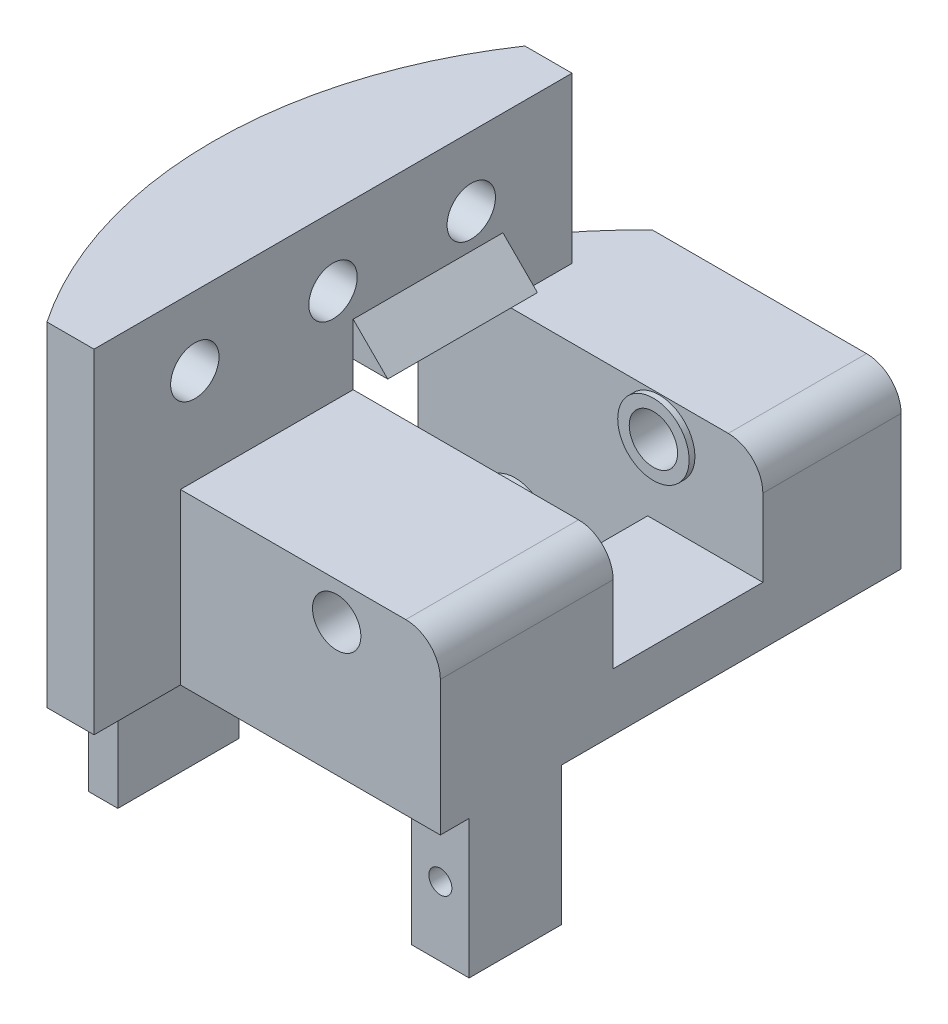
SolidWorks part; units mm, degrees
note: The reader was unsure of these and kept them because the rebuilt part matched: shared geometry of "Sketch24<2>".
material "Custom Plastic"
ref_plane "Front Plane" through (0, 0, 0) normal (0, 0, 1) x (1, 0, 0)
ref_plane "Top Plane" through (0, 0, 0) normal (0, 1, 0) x (1, 0, 0)
ref_plane "Right Plane" through (0, 0, 0) normal (1, 0, 0) x (0, 0, -1)
sketch "Sketch1" plane through (0, 0, 0) normal (0, 1, 0) x (1, 0, 0)
  line L12 (-36.9789, 1.25) -> (-36.9789, -1.25)
  line L13 (-36.9789, -1.25) -> (-31.9789, -1.25)
  line L14 (-31.9789, -1.25) -> (-31.9789, -17.25)
  line L15 (-31.9789, -17.25) -> (-8.9789, -17.25)
  line L16 (-8.9789, -17.25) -> (-8.9789, -1.25)
  line L17 (-8.9789, -1.25) -> (-3.9789, -1.25)
  line L18 (-3.9789, -1.25) -> (-3.9789, 1.25)
  line L19 (-3.9789, 1.25) -> (-8.9789, 1.25)
  line L20 (-8.9789, 1.25) -> (-8.9789, 5.25)
  line L21 (-8.9789, 5.25) -> (-31.9789, 5.25)
  line L22 (-31.9789, 5.25) -> (-31.9789, 1.25)
  line L23 (-31.9789, 1.25) -> (-36.9789, 1.25)
  line L24 (-31.9789, -17.25) -> (-32.7328, -17.25)
  line L25 (-8.9789, -9.25) -> (-3.9789, -9.25)
  line L26 (-3.9789, -9.25) -> (-3.9789, -1.25)
  line L27 (-34.5462, -13.25) -> (-31.9789, -13.25)
  circle A0 centre (0, 0) radius 37
  point P4 (-37, 0)
  point P15 (-36.9789, 0)
  dimension "D1" = 74
  dimension "D2" = 2.5
  dimension "D3" = 4
  dimension "D4" = 16
  dimension "D5" = 5
  dimension "D6" = 5
  dimension "D7" = 23
  dimension "D8" = 5
  dimension "D9" = 8
  dimension "D10" = 12
extrude "Boss-Extrude1" add sketch "Sketch1" along normal blind 12 contours L13 A0 L24 L14 | L25 L26 L17 L16
sketch "Sketch2" plane through (0, 12, 0) normal (0, 1, 0) x (1, 0, 0)
  line L3 (-3.9789, -13.25) -> (-3.9789, 1.75)
  line L6 (-3.9789, 1.75) -> (-36.9586, 1.75)
  line L7 (-34.5462, -13.25) -> (-3.9789, -13.25)
  line L8 (-8.9789, -1.25) -> (-3.9789, -1.25) construction
  line L9 (-3.9789, -9.25) -> (-3.9789, -1.25) construction
  arc A4 (-36.9586, 1.75) -> (-34.5462, -13.25) centre (0, 0) ccw
  arc A5 (-36.9789, -1.25) -> (-34.5462, -13.25) centre (0, 0) ccw construction
  dimension "D1" = 3
extrude "Boss-Extrude2" add sketch "Sketch2" along normal blind 17
hole_wizard "Ø2.0mm Dowel Hole1" positions "Sketch8" profile "Sketch9" hole size "Ø2.0" standard "ANSI Metric"
sketch "Sketch8" plane through (0, 0, 1.25) normal (0, 0, -1) x (-1, 0, 0)
  line L0 (8.9789, 12) -> (8.9789, 0) construction
  line L1 (8.9789, 0) -> (3.9789, 0) construction
  line L2 (36.9789, 0) -> (31.9789, 0) construction
  point P0 (6.4789, 6)
  point P2 (34.4789, 6)
  point P8 (8.9789, 6)
  point P11 (6.4789, 0)
  point P14 (34.4789, 0)
sketch "Sketch9" plane through (-6.4789, 6, 1.25) normal (1, 0, 0) x (0, 1, 0)
  line L0 (0, 0) -> (0, 8)
  line L1 (0, 8) -> (1, 8)
  line L2 (1, 8) -> (1, 0)
  line L5 (1, 0) -> (0, 0)
  line L10 (0, 8) -> (-1, 8) construction
  line L11 (0, -6.35) -> (0, 107.95) construction
  dimension "Hole Dia." = 2
  dimension "Hole Depth" = 8
  dimension "Drill Angle" = 180
sketch "Sketch13" plane through (0, 29, 0) normal (0, 1, 0) x (1, 0, 0)
  line L0 (-24.9586, 1.75) -> (-24.9586, 14.75)
  line L1 (-3.9789, 1.75) -> (-36.9586, 1.75) construction
  line L2 (-24.9586, 14.75) -> (-3.9789, 14.75)
  line L4 (-3.9789, 26.75) -> (-25.5624, 26.75)
  line L5 (-36.9586, 1.75) -> (-24.9586, 1.75)
  line L7 (-24.9586, 14.75) -> (-33.9328, 14.75)
  line L8 (-3.9789, 14.75) -> (-3.9789, 26.75)
  circle A0 centre (0, 0) radius 37
  arc A1 (-36.9586, 1.75) -> (-34.5462, -13.25) centre (0, 0) ccw construction
  dimension "D1" = 12
  dimension "D2" = 13
  dimension "D3" = 12
extrude "Boss-Extrude6" add sketch "Sketch13" against normal up to surface (17 mm away) contours L4 A0 L7 L2 L8 up to face at (-17.1799, 12, 4.65)
sketch "Sketch17" plane through (0, 29, 0) normal (0, 1, 0) x (1, 0, 0)
  line L1 (-34.5462, -13.25) -> (-26.5462, -13.25) construction
  line L2 (-26.5462, 20.75) -> (-26.5462, -20.75)
  line L5 (-26.5462, 20.75) -> (-30.6339, 20.75)
  line L6 (0, 0) -> (-37, 0) construction
  line L7 (-3.9789, 14.75) -> (-33.9328, 14.75) construction
  line L8 (-26.5462, -20.75) -> (-30.6339, -20.75)
  arc A4 (-30.6339, 20.75) -> (-30.6339, -20.75) centre (0, 0) ccw
  arc A5 (-36.9586, 1.75) -> (-34.5462, -13.25) centre (0, 0) ccw construction
  point P3 (0, 0)
  dimension "D1" = 8
  dimension "D2" = 6
extrude "Boss-Extrude8" add sketch "Sketch17" along normal blind 12
sketch "Sketch5" plane through (0, 0, 13.25) normal (0, 0, 1) x (1, 0, 0)
  line L0 (-31.9789, 12) -> (-3.9789, 12) construction
  line L2 (-3.9789, 29) -> (-3.9789, 12) construction
  circle A0 centre (-12.9789, 23.5) radius 2.1
  dimension "D3" = 4.2
  dimension "D1" = 11.5
  dimension "D2" = 9
extrude "Cut-Extrude2" cut sketch "Sketch5" against normal up to surface (40 mm away) up to face at (-14.7707, 20.5, -26.75)
sketch "Sketch19" plane through (0, 0, 13.25) normal (0, 0, 1) x (1, 0, 0)
  line L0 (-26.5462, 29) -> (-26.5462, 26.7)
  line L1 (-26.5462, 26.7) -> (-3.9789, 26.7)
  line L3 (-3.9789, 29) -> (-3.9789, 12) construction
  line L4 (-26.5462, 29) -> (-3.9789, 29) construction
  line L5 (-3.9789, 29) -> (-3.9789, 26.7)
  line L6 (-26.5462, 29) -> (-3.9789, 29)
  circle A3 centre (-12.9789, 23.5) radius 2.1 construction
  point P0 (-3.9789, 26.5639)
  dimension "D1" = 3.2
extrude "Cut-Extrude3" cut sketch "Sketch19" against normal up to surface (40 mm away)
sketch "Sketch22" plane through (0, 29, 0) normal (0, 1, 0) x (1, 0, 0)
  line L2 (-26.5462, 20.75) -> (-26.5462, 25.774)
  line L3 (-30.6339, 20.75) -> (-26.5462, 20.75)
  line L4 (-26.5462, 20.75) -> (-26.5462, 25.774)
  line L5 (-30.6339, 20.75) -> (-26.5462, 20.75)
  arc A1 (-26.5462, 25.774) -> (-30.6339, 20.75) centre (0, 0) ccw
  arc A2 (-26.5462, 25.774) -> (-30.6339, 20.75) centre (0, 0) ccw
  dimension "D1" = 0
extrude "Cut-Extrude5" cut sketch "Sketch22" against normal up to surface (2.3 mm away) up to face at (-17.3234, 26.7, -21.7557)
sketch "Sketch21" plane through (0, 12, 0) normal (0, -1, 0) x (1, 0, 0)
  line L0 (-33.9328, -14.75) -> (-3.9789, -14.75) construction
  line L1 (-3.9789, -1.75) -> (-13.9789, -1.75)
  line L2 (-3.9789, -1.75) -> (-3.9789, -14.75)
  line L3 (-3.9789, -14.75) -> (-13.9789, -14.75)
  line L4 (-13.9789, -1.75) -> (-13.9789, -14.75)
  line L5 (-3.9789, -1.75) -> (-36.9586, -1.75) construction
  point P7 (-3.9789, 1.25)
  dimension "D1" = 10
extrude "Boss-Extrude10" add sketch "Sketch21" against normal blind 5
fillet "Fillet3" radius 3 1 edges at (-3.9789, 26.7, 5.75)
sketch "Sketch23" plane through (0, 0, -1.75) normal (0, 0, -1) x (-1, 0, 0)
  circle A0 centre (12.9789, 23.5) radius 2.1 construction
  circle A1 centre (12.9789, 23.5) radius 2.1
  circle A2 centre (12.9789, 23.5) radius 3.1
  dimension "D1" = 1
extrude "Boss-Extrude11" add sketch "Sketch23" along normal blind 0.5
ref_plane "Plane3" through (0, 0, -8.25) normal (0, 0, 1) x (1, 0, 0)
mirror "Mirror4" about plane through (0, 0, -8.25) normal (0, 0, 1) of "Boss-Extrude11"
sketch "Sketch24" plane through (0, 0, 1.25) normal (0, 0, -1) x (-1, 0, 0)
  line L0 (31.9789, 0) -> (36.9789, 0) construction
  line L1 (36.9789, 0) -> (36.9789, 12) construction
  line L2 (36.9789, 12) -> (31.9789, 12) construction
  line L3 (31.9789, 12) -> (31.9789, 0) construction
  line L4 (3.9789, 0) -> (8.9789, 0) construction
  line L5 (8.9789, 0) -> (8.9789, 12) construction
  line L6 (8.9789, 12) -> (3.9789, 12) construction
  line L7 (3.9789, 12) -> (3.9789, 0) construction
  line L8 (31.9789, 0) -> (36.9789, 0)
  line L9 (36.9789, 0) -> (36.9789, 12)
  line L10 (36.9789, 12) -> (31.9789, 12)
  line L11 (31.9789, 12) -> (31.9789, 0)
  line L12 (3.9789, 0) -> (8.9789, 0)
  line L13 (8.9789, 0) -> (8.9789, 12)
  line L14 (8.9789, 12) -> (3.9789, 12)
  line L15 (3.9789, 12) -> (3.9789, 0)
  circle A0 centre (6.4789, 6) radius 1 construction
  circle A1 centre (6.4789, 6) radius 1
  circle A2 centre (34.4789, 6) radius 1 construction
  circle A3 centre (34.4789, 6) radius 1
extrude "Cut-Extrude6" cut sketch "Sketch24" against normal blind 1.5
extrude "Boss-Extrude12" add sketch "Sketch24<2>" against normal blind 1.5 from surface
sketch "Sketch24<2>" plane through (0, 0, 1.25) normal (0, 0, -1) x (-1, 0, 0) same geometry as "Sketch24"
hole_wizard "Ø2.0mm Dowel Hole2" positions "Sketch25" profile "Sketch26" hole size "Ø2.0" standard "ANSI Metric" end condition through all
sketch "Sketch25" plane through (-26.5462, 0, 0) normal (1, 0, 0) x (0, 0, -1)
  line L0 (-20.75, 41) -> (-20.75, 29) construction
  point P0 (-12, 35)
  point P2 (0, 35)
  point P4 (12, 35)
  point P8 (0, 0)
  point P11 (-20.75, 35)
  dimension "D1" = 12
  dimension "D2" = 12
sketch "Sketch26" plane through (-26.5462, 35, 12) normal (0, 1, 0) x (0, 0, -1)
  line L0 (0, 0) -> (0, 10.4538)
  line L1 (0, 10.4538) -> (2.1, 10.4538)
  line L2 (2.1, 10.4538) -> (2.1, 0)
  line L5 (2.1, 0) -> (0, 0)
  line L11 (0, -6.35) -> (0, 107.95) construction
  dimension "Thru Hole Dia." = 4.2
  dimension "Thru Hole Depth" = 10.4538
sketch "Sketch27" plane through (0, 29, 0) normal (0, -1, 0) x (1, 0, 0)
  line L3 (-34.5462, 13.25) -> (-26.5462, 13.25)
  line L4 (-26.5462, 13.25) -> (-26.5462, 20.75)
  line L5 (-26.5462, 20.75) -> (-30.6339, 20.75)
  line L6 (-34.5462, 13.25) -> (-26.5462, 13.25)
  line L7 (-26.5462, 13.25) -> (-26.5462, 20.75)
  line L8 (-26.5462, 20.75) -> (-30.6339, 20.75)
  arc A1 (-30.6339, 20.75) -> (-34.5462, 13.25) centre (0, 0) ccw
  arc A2 (-30.6339, 20.75) -> (-34.5462, 13.25) centre (0, 0) ccw
  dimension "D1" = 0
extrude "Boss-Extrude13" add sketch "Sketch27" along normal up to surface (17 mm away) up to face at (-18.5577, 12, -1.9941)
sketch "Sketch28" plane through (0, 0, -1.75) normal (0, 0, -1) x (-1, 0, 0)
  line L0 (26.5462, 29) -> (23.5462, 29)
  line L1 (23.5462, 29) -> (26.5462, 32)
  line L2 (26.5462, 41) -> (26.5462, 26.7) construction
  line L3 (26.5462, 29) -> (26.5462, 32)
  dimension "D1" = 3
  dimension "D2" = 3
extrude "Boss-Extrude14" add sketch "Sketch28" along normal up to surface (13 mm away) up to face at (-16.0789, 23.5, -14.75)
